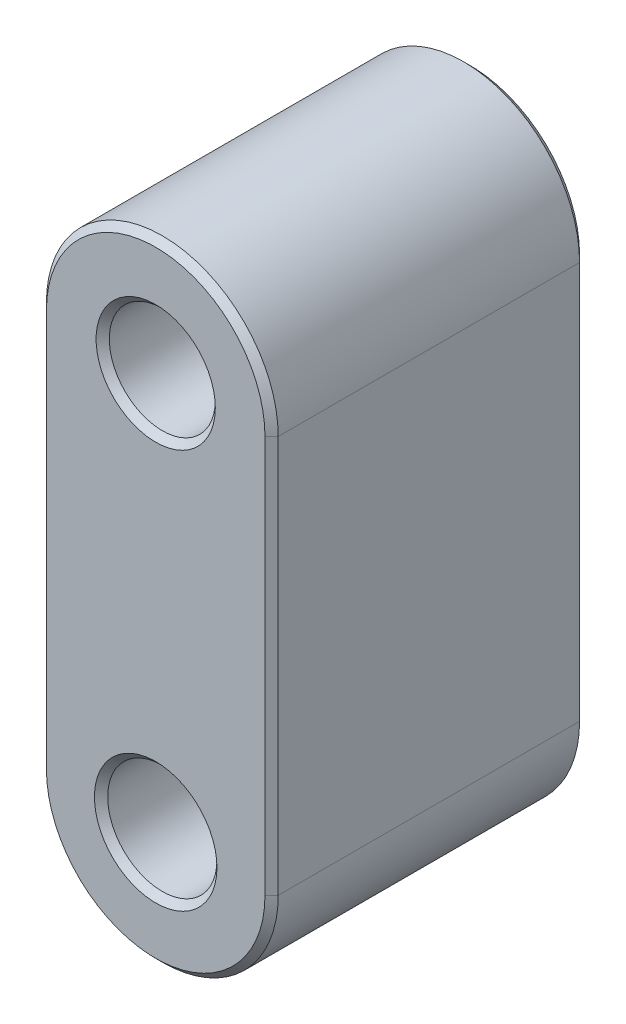
SolidWorks part; units mm, degrees
ref_plane "Front" through (0, 0, 0) normal (0, 0, 1) x (1, 0, 0)
ref_plane "Top" through (0, 0, 0) normal (0, 1, 0) x (1, 0, 0)
ref_plane "Right" through (0, 0, 0) normal (1, 0, 0) x (0, 0, -1)
sketch "Sketch1" plane through (0, 0, 0) normal (0, 0, 1) x (1, 0, 0)
  line L3 (-3.5, 0) -> (-1.6, 0) construction
  line L23 (1.65, -12) -> (3.55, -12) construction
  line L33 (-3.5, 0) -> (-3.5, -12)
  line L34 (3.5, -12) -> (3.5, 0)
  circle A0 centre (0, 0) radius 3.5 construction
  circle A3 centre (0, 0) radius 1.6
  circle A12 centre (0, -12) radius 1.65
  circle A13 centre (0, -12) radius 4.25 construction
  arc A22 (-3.5, 0) -> (3.5, 0) centre (0, 0) cw
  arc A28 (-3.5, -12) -> (3.5, -12) centre (0, -12) ccw
  dimension "D1" = 3.2
  dimension "D3" = 8.5
  dimension "D6" = 3.3
  dimension "D7" = 3.5
  dimension "D2" = 1.9
  dimension "D5" = 12
extrude "Boss-Extrude1" add sketch "Sketch1" along normal mid plane 9.5 contours A3 region at (0, -5.9711, 0)
sketch "Sketch2" plane through (0, 0, 0) normal (0, 0, 1) x (1, 0, 0)
  line L0 (-3.493, -12.2218) -> (-4.3556, 1.3622)
  line L1 (0, 0) -> (0, 8.0844) construction
  line L2 (0, 0) -> (-0.4318, 1.6114) construction
  line L3 (-0.4318, 1.6114) -> (-1.2941, 4.8296) construction
  line L4 (-1.2941, 4.8296) -> (-1.4494, 5.4092) construction
  line L5 (3.5, 1.6114) -> (3.5, -12)
  line L6 (3.5, -12) -> (3.5, 0) construction
  line L7 (3.5, -12) -> (3.5, 0) construction
  arc A0 (-4.3556, 1.3622) -> (3.5, 1.6114) centre (-0.4318, 1.6114) cw
  circle A1 centre (0, 0) radius 5 construction
  arc A2 (-3.5, -12) -> (3.5, -12) centre (0, -12) ccw construction
  dimension "D2" = 10
  dimension "D1" = 0.6
  dimension "D3" = 15
extrude "Spring" [suppressed] add sketch "Sketch2" along normal through all and the other way through all thin thin type one direction wall 1
fillet "Spring Inside Fillets" [suppressed] radius 0.25
chamfer "Deburs" [suppressed] distance 0.2 angle 45
sketch "Sketch3" [suppressed] plane through (-4.0649, -0.1931, 0) normal (-0.9989, -0.0475, 0) x (0, 0, 1)
  line L1 (0, -0.6005) -> (0, -9.4865) construction
  line L6 (4.55, 1.8995) -> (-4.55, 1.8995) construction
  line L8 (4.55, -11.9865) -> (-4.55, -11.9865) construction
  dimension "D1" = 2.5
  dimension "D2" = 2.5
sketch "Sketch4" [suppressed] plane through (-4.0649, -0.1931, 0) normal (-0.9989, -0.0475, 0) x (0, 0, 1)
  line L0 (0, -0.6005) -> (0, -9.4865)
  line L1 (-2, -2.6005) -> (0, -0.6005)
  line L2 (0, -0.6005) -> (2, -2.6005)
  line L3 (0, -0.6005) -> (0, -9.4865) construction
  line L6 (0, -12.0651) -> (0, -0.0719) construction
  dimension "D1" = 45
  dimension "D2" = 2
extrude "Arrow Point" [suppressed] add sketch "Sketch4" along normal blind 0.2 draft 55 thin contours L1 | L2 thin type one direction wall 0.8
sketch "Sketch5" [suppressed] plane through (-4.0649, -0.1931, 0) normal (-0.9989, -0.0475, 0) x (0, 0, 1)
  line L0 (0, -1.0045) -> (0, -9.4865)
  line L1 (0, -0.6005) -> (0, -9.4865) construction
extrude "Arrow Shaft" [suppressed] add sketch "Sketch5" along normal blind 0.2 draft 55 thin thin type mid plane wall 0.8
chamfer "Deburs no Spring" distance 0.2 angle 45 12 edges at (0, -15.5, -4.75) (3.5, -6, -4.75) (0, 3.5, -4.75) (-3.5, -6, -4.75) (1.65, -12, -4.75) (1.6, 0, -4.75) (0, 3.5, 4.75) (3.5, -6, 4.75) (0, -15.5, 4.75) (-3.5, -6, 4.75) (1.65, -12, 4.75) (1.6, 0, 4.75)
equation "\"D1@Sketch1\"=\"Clearance Hole Diameter@Box Assy.Assembly\"+.05mm"
equation "\"D6@Sketch1\"=\"Clearance Hole Diameter@Box Assy.Assembly\"+.15mm"
